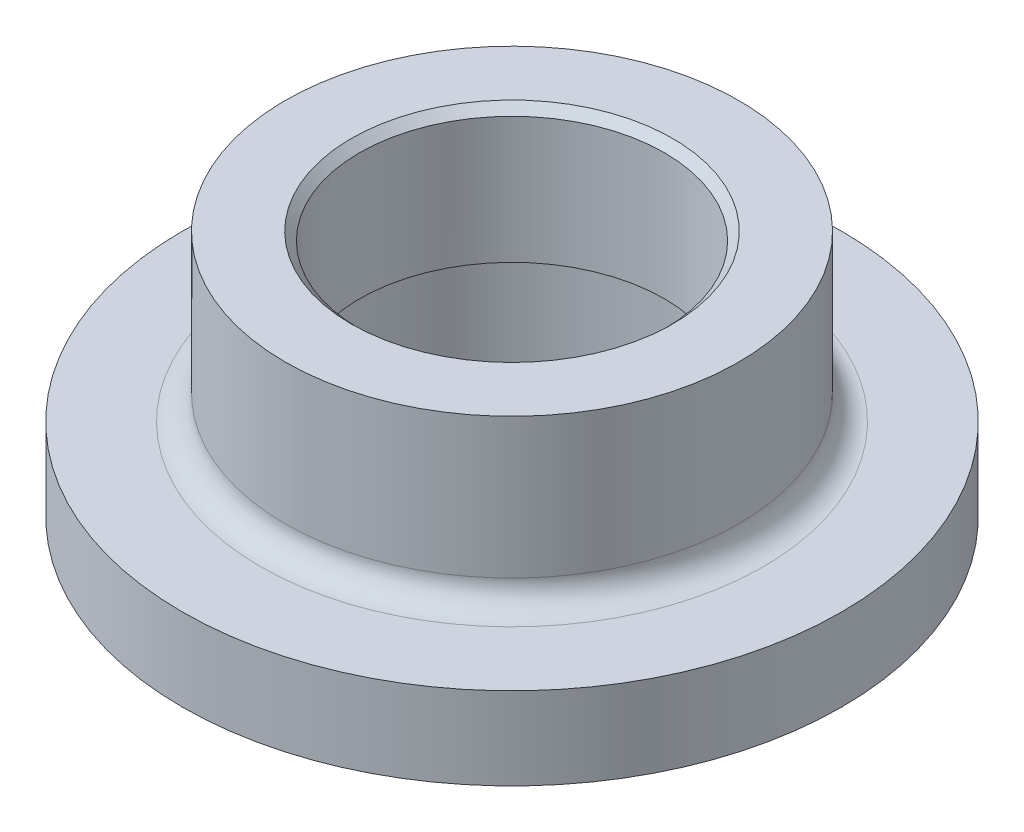
SolidWorks part; units mm, degrees
material "ABS"
ref_plane "Front Plane" through (0, 0, 0) normal (0, 0, 1) x (1, 0, 0)
ref_plane "Top Plane" through (0, 0, 0) normal (0, 1, 0) x (1, 0, 0)
ref_plane "Right Plane" through (0, 0, 0) normal (1, 0, 0) x (0, 0, -1)
sketch "Sketch1" plane through (0, 0, 0) normal (0, 1, 0) x (1, 0, 0)
  circle A0 centre (0, 0) radius 8
  circle A1 centre (0, 0) radius 3.7
  dimension "D1" = 16
  dimension "D2" = 7.4
extrude "Boss-Extrude1" add sketch "Sketch1" along normal blind 2
sketch "Sketch2" plane through (0, 2, 0) normal (0, 1, 0) x (1, 0, 0)
  circle A0 centre (0, 0) radius 3.7
  circle A1 centre (0, 0) radius 5.5
  dimension "D1" = 11
  dimension "D2" = 7.4
extrude "Boss-Extrude2" add sketch "Sketch2" along normal blind 4
fillet "Fillet2" radius 0.6 1 edges at (0, 2, 5.5)
chamfer "Chamfer2" distance 0.2 angle 45 1 edges at (0, 6, 3.7)
sketch "Sketch3" plane through (0, 0, 0) normal (0, -1, 0) x (1, 0, 0)
  circle A0 centre (0, 0) radius 4.1
  dimension "D1" = 8.2
extrude "Cut-Extrude1" cut sketch "Sketch3" against normal blind 2.5
chamfer "Chamfer3" distance 0.4 angle 30 1 edges at (0, 2.5, -3.7) first distance on face at (0, 2.5, -3.7)
